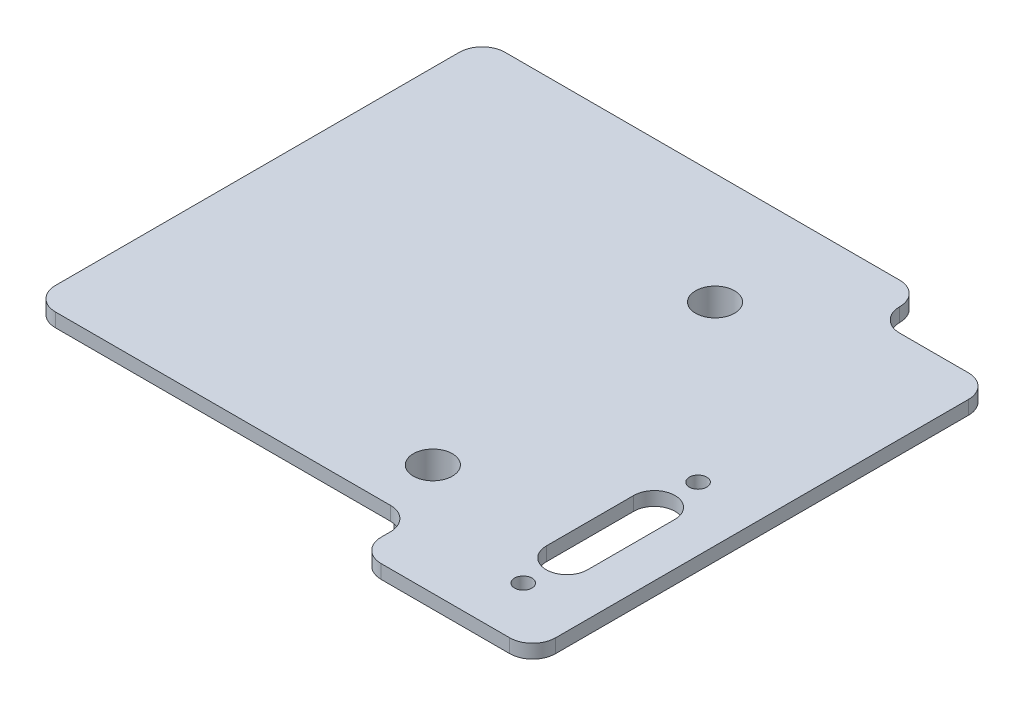
SolidWorks part; units mm, degrees
ref_plane "Front Plane" through (0, 0, 0) normal (0, 0, 1) x (1, 0, 0)
ref_plane "Top Plane" through (0, 0, 0) normal (0, 1, 0) x (1, 0, 0)
ref_plane "Right Plane" through (0, 0, 0) normal (1, 0, 0) x (0, 0, -1)
sketch "Sketch1" plane through (0, 0, 0) normal (0, 1, 0) x (1, 0, 0)
  line L0 (0, 0) -> (83, 0)
  line L1 (83, 0) -> (83, -12)
  line L2 (83, -12) -> (121, -12)
  line L3 (121, -12) -> (121, 88)
  line L5 (0, 98) -> (0, 0)
  line L6 (0, 43) -> (121, 43) construction
  line L7 (75, 73.75) -> (75, 12.25) construction
  line L8 (0, 98) -> (96, 98)
  line L9 (96, 98) -> (96, 88)
  line L10 (96, 88) -> (121, 88)
  line L11 (86.8502, -12) -> (86.8502, 98) construction
  point P11 (75, 43)
  point P13 (75, 73.75)
  point P14 (75, 12.25)
  point P18 (86.8502, 43)
  dimension "D1" = 121
  dimension "D2" = 110
  dimension "D3" = 38
  dimension "D4" = 12
  dimension "D5" = 61.5
  dimension "D6" = 8
  dimension "D7" = 10
  dimension "D8" = 25
extrude "plate" add sketch "Sketch1" along normal blind 3
sketch "Sketch2" plane through (0, 3, 0) normal (0, 1, 0) x (1, 0, 0)
  circle A0 centre (75, 73.75) radius 6
  circle A1 centre (75, 12.25) radius 6
  dimension "D1" = 12
extrude "mount posts" add sketch "Sketch2" against normal blind 22
sketch "Sketch3" plane through (0, 3, 0) normal (0, 1, 0) x (1, 0, 0)
  circle A0 centre (75, 73.75) radius 4.25
  circle A1 centre (75, 12.25) radius 4.25
  dimension "D1" = 8.5
extrude "mount cbore" cut sketch "Sketch3" against normal blind 19.5
hole_wizard "#8 Clearance Hole1" positions "Sketch4" profile "Sketch5" hole size "#8" standard "ANSI Inch" end condition through all
sketch "Sketch4" plane through (0, -16.5, 0) normal (0, 1, 0) x (1, 0, 0)
  circle A0 centre (75, 12.25) radius 4.25 construction
  circle A1 centre (75, 73.75) radius 4.25 construction
  point P0 (75, 73.75)
  point P2 (75, 12.25)
sketch "Sketch5" plane through (75, -16.5, -73.75) normal (1, 0, 0) x (0, 0, 1)
  line L0 (0, 0) -> (0, 2.5)
  line L1 (0, 2.5) -> (2.2479, 2.5)
  line L2 (2.2479, 2.5) -> (2.2479, 0)
  line L5 (2.2479, 0) -> (0, 0)
  line L11 (0, -6.35) -> (0, 107.95) construction
  dimension "Thru Hole Dia." = 4.4958
  dimension "Thru Hole Depth" = 2.5
ref_plane "mid plane" through (0, 0, -43) normal (0, 0, -1) x (1, 0, 0)
sketch "Sketch8" plane through (0, 0, -43) normal (0, 0, -1) x (1, 0, 0)
  line L0 (45.25, 0) -> (46.85, 0)
  line L1 (0, 0) -> (121, 0) construction
  line L2 (45.25, 0) -> (43.5, 29)
  line L3 (43.5, 29) -> (45.1, 29)
  line L4 (45.1, 29) -> (46.85, 0)
  line L5 (40, 0) -> (40, 41.9178) construction
  point P9 (44.3, 29)
  dimension "D1" = 1.6
  dimension "D2" = 3.5
  dimension "D3" = 29
  dimension "D4" = 5.25
  dimension "D5" = 40
revolve "foot" add sketch "Sketch8" angle 360 about L5
fillet "Fillet1" radius 1.5 2 edges at (40, 0, -37.75) (40, 0, -36.15)
sketch "Sketch7" plane through (0, 3, 0) normal (0, 1, 0) x (1, 0, 0)
  line L0 (107.15, 87.7375) -> (107.15, 106.2625) construction
  line L1 (121, -12) -> (121, 88) construction
  line L2 (83, -12) -> (121, -12) construction
  line L3 (115, 18.85) -> (99.3, 18.85) construction
  line L4 (102.65, 9.325) -> (102.65, 28.375)
  line L5 (99.3, -6) -> (99.3, 43.7) construction
  line L6 (99.3, -6) -> (115, -6) construction
  line L7 (115, -6) -> (115, 43.7) construction
  line L8 (99.3, 43.7) -> (115, 43.7) construction
  line L9 (99.3, -6) -> (115, 43.7) construction
  line L10 (115, -6) -> (99.3, 43.7) construction
  line L11 (111.65, 9.325) -> (111.65, 28.375)
  circle A0 centre (107.15, 9.325) radius 4.5 construction
  circle A1 centre (107.15, 28.375) radius 4.5 construction
  arc A2 (102.65, 9.325) -> (111.65, 9.325) centre (107.15, 9.325) ccw
  arc A3 (102.65, 28.375) -> (111.65, 28.375) centre (107.15, 28.375) cw
  circle A4 centre (107.15, 37.9) radius 1.9
  circle A5 centre (107.15, -0.2) radius 1.9
  point P16 (107.15, 18.85)
  point P19 (102, -12)
  dimension "D2" = 19.05
  dimension "D5" = 9
  dimension "D6" = 3.8
  dimension "D1" = 49.7
  dimension "D3" = 6
  dimension "D4" = 15.7
  dimension "D7" = 38.1
  dimension "D8" = 6
extrude "terminal strip" cut sketch "Sketch7" against normal through all
chamfer "Chamfer1" distance 3 angle 45 2 edges at (75, -16.5, -69.5) (75, -16.5, -8)
chamfer "Chamfer2" distance 1 angle 45 2 edges at (75, -19, -6.25) (75, -19, -67.75)
fillet "Fillet3" radius 1.5 2 edges at (75, 0, -67.75) (75, 0, -6.25)
fillet "corners" radius 5 8 edges at (0, 1.5, -98) (96, 1.5, -98) (96, 1.5, -88) (121, 1.5, -88) (121, 1.5, 12) (83, 1.5, 12) (83, 1.5, 0) (0, 1.5, 0)
